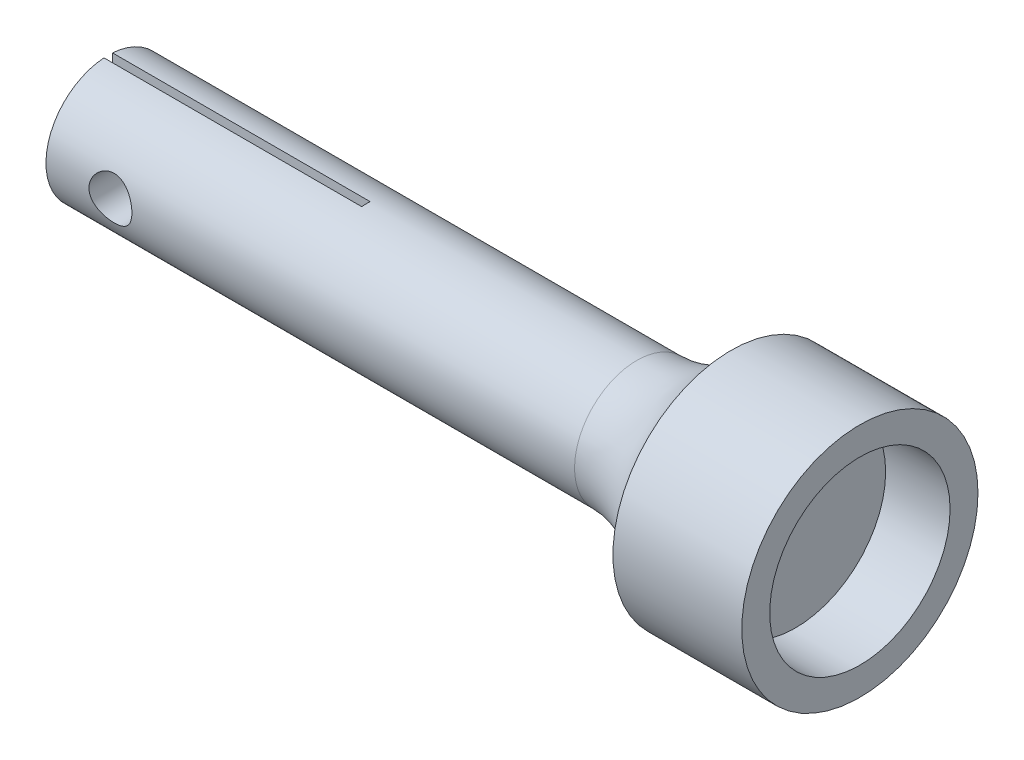
SolidWorks part; units mm, degrees
ref_plane "前视基准面" through (0, 0, 0) normal (0, 0, 1) x (1, 0, 0)
ref_plane "上视基准面" through (0, 0, 0) normal (0, 1, 0) x (1, 0, 0)
ref_plane "右视基准面" through (0, 0, 0) normal (1, 0, 0) x (0, 0, -1)
other "Configuration Table"
sketch "草图1" plane through (0, 0, 0) normal (1, 0, 0) x (0, 0, -1)
  circle A0 centre (0, 0) radius 2.9
  dimension "D1" = 5.8
extrude "凸台-拉伸1" add sketch "草图1" along normal blind 35
sketch "草图2" plane through (0, 0, 0) normal (-1, 0, 0) x (0, 0, 1)
  line L0 (0, 2.9) -> (0, -2.9) construction
  line L2 (-0.2, 3.1215) -> (0.2, 3.1215)
  line L3 (-0.2, 3.1215) -> (-0.2, -2.329)
  line L4 (-0.2, -2.329) -> (0.2, -2.329)
  line L5 (0.2, 3.1215) -> (0.2, -2.329)
  circle A0 centre (0, 0) radius 2.9 construction
  dimension "D1" = 0.4
  dimension "D2" = 0.2
extrude "切除-拉伸1" cut sketch "草图2" against normal blind 12
sketch "草图3" plane through (0, 0, 0.2) normal (0, 0, -1) x (-1, 0, 0)
  line L0 (0, -0.0035) -> (-6.0327, -0.0035) construction
  line L1 (0, -2.9) -> (0, 2.8931) construction
  circle A0 centre (-3, -0.0035) radius 1
  dimension "D1" = 2
  dimension "D2" = 3
extrude "切除-拉伸2" cut sketch "草图3" against normal blind 10 and the other way blind 10
sketch "草图4" plane through (35, 0, 0) normal (1, 0, 0) x (0, 0, -1)
  circle A0 centre (0, 0) radius 5.5
  dimension "D1" = 11
extrude "凸台-拉伸2" add sketch "草图4" against normal blind 6
sketch "草图5" plane through (35, 0, 0) normal (1, 0, 0) x (0, 0, -1)
  circle A0 centre (0, 0) radius 4.2
  dimension "D1" = 8.4
extrude "切除-拉伸3" cut sketch "草图5" against normal blind 3
fillet "圆角1" radius 5 1 edges at (29, 0, -2.9)
